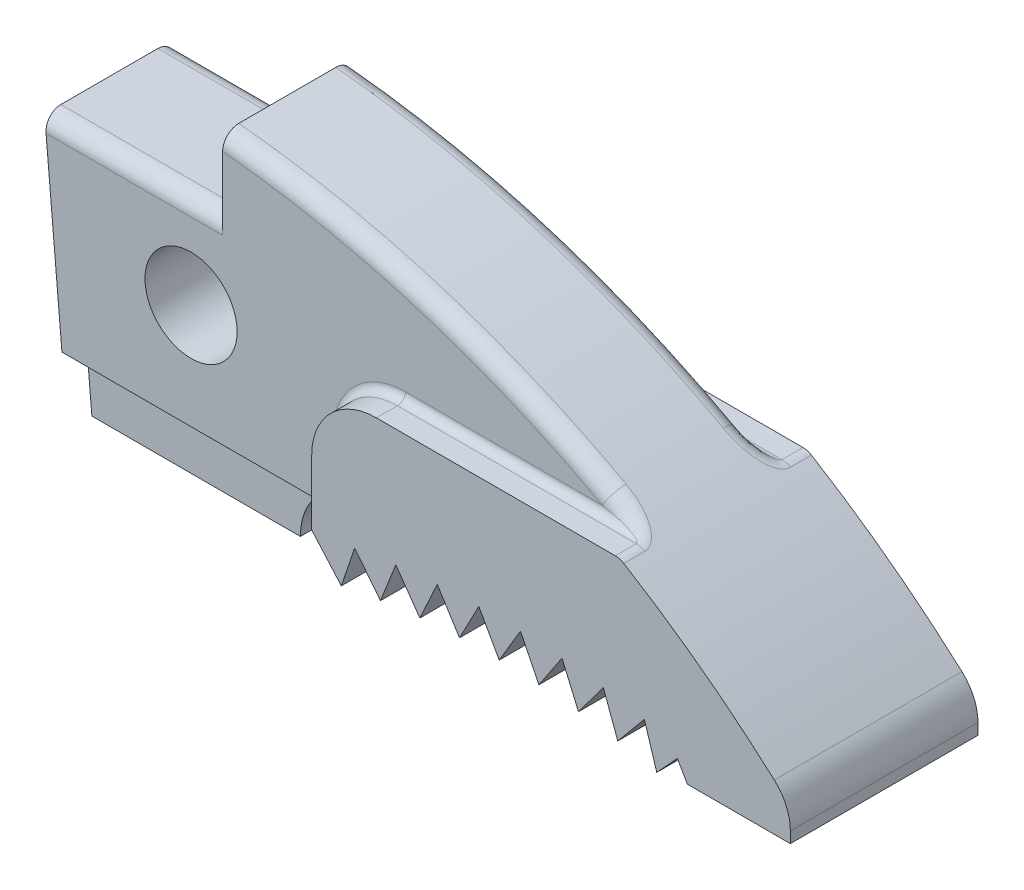
SolidWorks part; units mm, degrees
note: '?' marks a value the reader was unsure of.
ref_plane "Front Plane" through (0, 0, 0) normal (0, 0, 1) x (1, 0, 0)
ref_plane "Top Plane" through (0, 0, 0) normal (0, 1, 0) x (1, 0, 0)
ref_plane "Right Plane" through (0, 0, 0) normal (1, 0, 0) x (0, 0, -1)
sketch "Sketch1" plane through (0, 0, 0) normal (0, 0, 1) x (1, 0, 0)
  line L0 (0, 0) -> (0, 50.8039) construction
  line L1 (0, 0) -> (47.4869, 47.4869) construction
  line L2 (0, 0) -> (-4.2741, 48.8536) construction
  line L3 (-24.9861, 25.7175) -> (66.7901, 25.7175) construction
  line L4 (-3.459, 39.5365) -> (-2.25, 25.7175)
  line L5 (-2.25, 25.7175) -> (5.8796, 25.7175)
  line L6 (5.8796, 25.7175) -> (5.8796, 26.3525)
  line L7 (8.4196, 28.8925) -> (27.2088, 28.8925)
  circle A0 centre (0, 0) radius 39.6875 construction
  arc A1 (27.2088, 28.8925) -> (-3.459, 39.5365) centre (0, 0) ccw
  arc A2 (8.4196, 28.8925) -> (5.8796, 26.3525) centre (8.4196, 26.3525) ccw
  point P16 (5.8796, 28.8925)
  dimension "D1" = 79.375
  dimension "D4" = 13.97
  dimension "D8" = 2.54
  dimension "D2" = 45
  dimension "D3" = 5
  dimension "D5" = 5.8796
  dimension "D6" = 3.175
  dimension "D7" = 21.3292
extrude "Extrude1" add sketch "Sketch1" along normal mid plane 3.175
sketch "Sketch2" plane through (0, 0, 0) normal (0, 0, 1) x (1, 0, 0)
  line L0 (8.4196, 28.8925) -> (-2.5278, 28.8925)
  line L4 (-3.459, 39.5365) -> (-2.25, 25.7175)
  line L5 (-2.25, 25.7175) -> (5.8796, 25.7175)
  line L6 (5.8796, 25.7175) -> (5.8796, 26.3525)
  line L7 (8.4196, 28.8925) -> (27.2088, 28.8925)
  line L8 (-3.459, 39.5365) -> (-2.5278, 28.8925)
  line L11 (8.4196, 28.8925) -> (27.2088, 28.8925)
  arc A2 (27.2088, 28.8925) -> (-3.459, 39.5365) centre (0, 0) ccw
  arc A3 (8.4196, 28.8925) -> (5.8796, 26.3525) centre (8.4196, 26.3525) ccw
  arc A4 (27.2088, 28.8925) -> (-3.459, 39.5365) centre (0, 0) ccw
  dimension "D1" = 0
extrude "Extrude2" add sketch "Sketch2" along normal mid plane 5.08
sketch "Sketch3" plane through (0, 0, 0) normal (0, 0, 1) x (1, 0, 0)
  line L2 (27.2088, 28.8925) -> (8.4196, 28.8925)
  line L4 (20.5175, 33.9725) -> (8.4196, 33.9725)
  line L5 (8.4196, 28.8925) -> (8.4196, 33.9725)
  arc A0 (27.2088, 28.8925) -> (-3.459, 39.5365) centre (0, 0) ccw construction
  arc A1 (27.2088, 28.8925) -> (20.5175, 33.9725) centre (0, 0) ccw
  dimension "D1" = 5.08
extrude "Extrude3" add sketch "Sketch3" along normal mid plane 7.366
sketch "Sketch7" plane through (0, 0, 3.683) normal (0, 0, 1) x (1, 0, 0)
  line L0 (8.4196, 28.8925) -> (27.2088, 28.8925) construction
  line L1 (8.4196, 28.8925) -> (22.4336, 28.8925)
  arc A0 (8.4196, 28.8925) -> (22.4336, 28.8925) centre (15.4266, -1.6318) cw
  dimension "D1" = 31.3182
  dimension "D2" = 4.7752
extrude "Cut-Extrude1" cut sketch "Sketch7" against normal through all
sketch "Sketch4" plane through (0, 0, 0) normal (0, 0, 1) x (1, 0, 0)
  line L0 (8.4196, 28.8925) -> (9.5815, 27.5708)
  line L1 (9.5815, 27.5708) -> (10.1451, 29.2379)
  line L3 (9.5815, 27.5708) -> (9.2893, 29.0307) construction
  line L5 (8.4196, 33.9725) -> (8.4196, 28.8925) construction
  arc A1 (22.4336, 28.8925) -> (8.4196, 28.8925) centre (15.4266, -1.6318) ccw construction
  arc A2 (10.1451, 29.2379) -> (8.4196, 28.8925) centre (15.4266, -1.6318) ccw
  dimension "D1" = 30
  dimension "D2" = 30
  dimension "D4" = 1.7598
extrude "Extrude4" add sketch "Sketch4" along normal up to surface and the other way up to surface up to face at (17.4268, 31.1188, 3.683) other way up to face at (17.4268, 31.1188, -3.683)
ref_axis "Axis1" through (15.4266, -1.6318, 3.683) along (0, 0, -1)?
pattern_circular "CirPattern1" count 9 every 3 about axis through (15.4266, -1.6318, 0) along (0, 0, 1) of "Extrude4"
sketch "Sketch10" plane through (0, 0, 2.54) normal (0, 0, 1) x (1, 0, 0)
  line L1 (-7.2341, 44.5224) -> (3.7813, 44.5224)
  line L2 (-7.2341, 44.5224) -> (-7.2341, 36.6535)
  line L3 (-7.2341, 36.6535) -> (3.7813, 36.6535)
  line L4 (3.7813, 44.5224) -> (3.7813, 36.6535)
extrude "Cut-Extrude4" cut sketch "Sketch10" against normal through all
fillet "Fillet5" radius 2.54 2 edges at (8.4196, 33.9725, -3.1115) (8.4196, 33.9725, 3.1115)
fillet "Fillet4" radius 0.3175 6 edges at (15.7385, 33.9725, 2.54) (8.4196, 30.1625, 2.54) (8.4196, 30.1625, -2.54) (15.7385, 33.9725, -2.54) (9.1635, 33.2286, -2.54) (9.1635, 33.2286, 2.54)
fillet "Fillet6" radius 0.635 10 edges at (20.5175, 33.9725, 3.2702) (20.4507, 34.0128, 2.7028) (12.1648, 37.7772, 2.54) (20.5175, 33.9725, -3.2702) (20.4783, 33.9961, -2.7373) (2.9459, 28.8925, -1.5875) (2.9459, 28.8925, 1.5875) (12.1648, 37.7772, -2.54) (0.2873, 36.6535, -2.54) (0.2873, 36.6535, 2.54)
sketch "Sketch5" plane through (0, 28.8925, 0) normal (0, -1, 0) x (1, 0, 0)
  line L4 (22.4336, 3.683) -> (22.4336, -3.683)
  line L5 (22.4336, -3.683) -> (27.2088, -3.683)
  line L6 (27.2088, -3.683) -> (27.2088, 3.683)
  line L7 (27.2088, 3.683) -> (22.4336, 3.683)
  line L8 (22.4336, 3.683) -> (22.4336, -3.683)
  line L9 (22.4336, -3.683) -> (27.2088, -3.683)
  line L10 (27.2088, -3.683) -> (27.2088, 3.683)
  line L11 (27.2088, 3.683) -> (22.4336, 3.683)
  dimension "D1" = 0
extrude "Extrude5" add sketch "Sketch5" along normal blind 1.27
chamfer "Chamfer1" distance 1.27 angle 30 1 edges at (22.4336, 27.6225, 0)
fillet "Fillet7" radius 1.905 1 edges at (27.2088, 28.8925, 0)
sketch "Sketch9" plane through (5.8796, 0, 0) normal (1, 0, 0) x (0, 0, -1)
  line L4 (1.5875, 25.7175) -> (1.5875, 26.3525)
  line L5 (1.5875, 26.3525) -> (-1.5875, 26.3525)
  line L6 (-1.5875, 26.3525) -> (-1.5875, 25.7175)
  line L7 (-1.5875, 25.7175) -> (1.5875, 25.7175)
  line L8 (1.5875, 25.7175) -> (1.5875, 26.3525)
  line L9 (1.5875, 26.3525) -> (-1.5875, 26.3525)
  line L10 (-1.5875, 26.3525) -> (-1.5875, 25.7175)
  line L11 (-1.5875, 25.7175) -> (1.5875, 25.7175)
  dimension "D1" = 0
extrude "Cut-Extrude3" cut sketch "Sketch9" against normal through all
sketch "Sketch11" plane through (0, 0, -2.54) normal (0, 0, -1) x (-1, 0, 0)
  circle A0 centre (-2.54, 33.02) radius 1.8079
  dimension "D1" = 2.54
  dimension "D2" = 33.02
extrude "Cut-Extrude5" cut sketch "Sketch11" against normal blind 8.636
